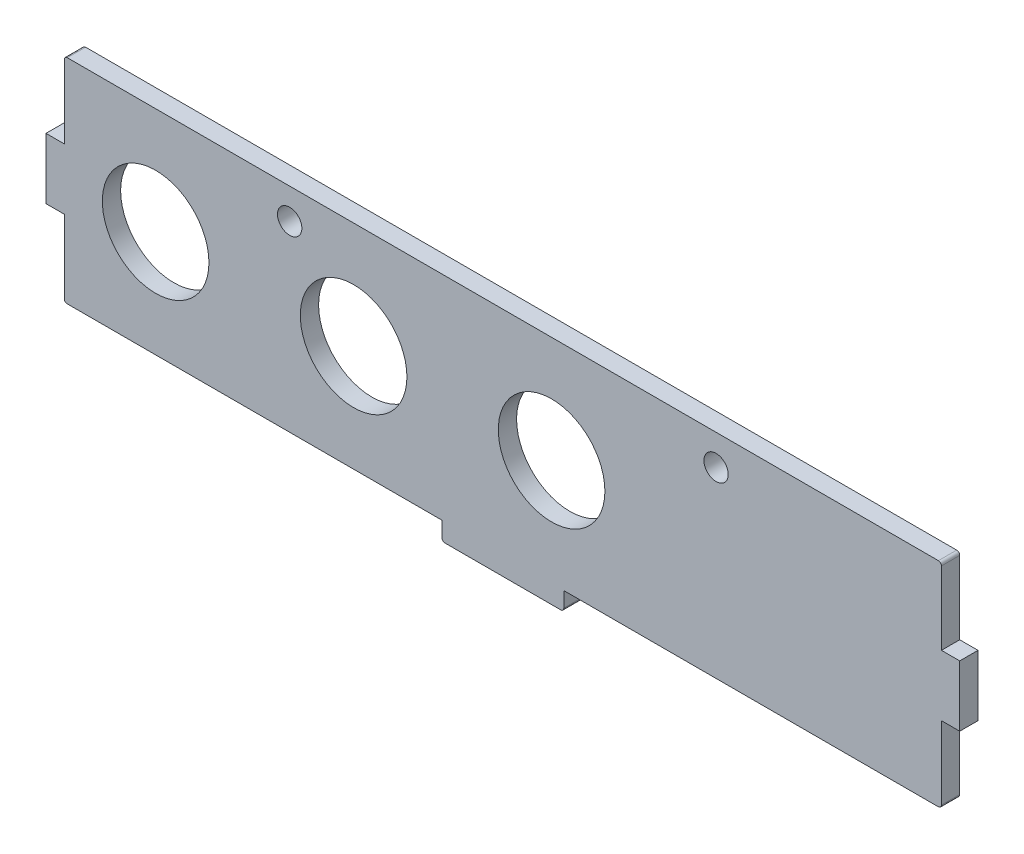
SolidWorks part; units mm, degrees
material "Beech"
ref_plane "Спереди" through (0, 0, 0) normal (0, 0, 1) x (1, 0, 0)
ref_plane "Сверху" through (0, 0, 0) normal (0, 1, 0) x (1, 0, 0)
ref_plane "Справа" through (0, 0, 0) normal (1, 0, 0) x (0, 0, -1)
sketch "Sketch1" plane through (0, 0, 0) normal (0, 0, 1) x (1, 0, 0)
  line L1 (0, 0) -> (300, 0)
  line L2 (0, 0) -> (0, 70)
  line L3 (0, 70) -> (300, 70)
  line L4 (300, 0) -> (300, 70)
  dimension "D1" = 70
  dimension "D2" = 300
extrude "front" add sketch "Sketch1" against normal blind 6
sketch "Sketch2" plane through (0, 0, 0) normal (0, 0, 1) x (1, 0, 0)
  line L0 (6, 70) -> (6, 45)
  line L1 (300, 70) -> (0, 70) construction
  line L2 (6, 45) -> (0, 45)
  line L3 (0, 70) -> (0, 0) construction
  line L4 (0, 25) -> (6, 25)
  line L5 (6, 25) -> (6, 0)
  line L6 (0, 0) -> (300, 0) construction
  line L7 (0, 45) -> (0, 25)
  line L8 (6, 70) -> (0, 70)
  line L9 (0, 70) -> (0, 45)
  line L10 (80, 60) -> (220, 60) construction
  line L11 (0, 25) -> (0, 0)
  line L12 (0, 0) -> (6, 0)
  line L13 (294, 70) -> (294, 45)
  line L14 (294, 45) -> (300, 45)
  line L15 (300, 0) -> (300, 70) construction
  line L16 (300, 45) -> (300, 70)
  line L17 (300, 70) -> (294, 70)
  line L18 (300, 25) -> (294, 25)
  line L19 (294, 25) -> (294, 0)
  line L20 (294, 0) -> (300, 0)
  line L21 (300, 0) -> (300, 25)
  circle A0 centre (80, 60) radius 4
  circle A1 centre (220, 60) radius 4
  point P32 (150, 60)
  point P33 (150, 70)
  line M1 (0, 70) -> (0, 0)
  line M2 (0, 0) -> (300, 0)
  line M4 (300, 70) -> (0, 70)
  dimension "D3" = 8
  dimension "D4" = 10
  dimension "D1" = 6
  dimension "D2" = 20
  dimension "D5" = 140
extrude "mount" cut sketch "Sketch2" against normal through all contours L2 L0 M4 M1 | L5 L4 M1 M2 | L16 L17 L13 L14 | L21 L18 L19 L20 | A0 | A1 region at (3, 12.5, 0) region at (3, 57.5, 0)
sketch "Sketch4" plane through (0, 0, 0) normal (0, 0, 1) x (1, 0, 0)
  line L0 (6, 0) -> (294, 0) construction
  line L1 (130, 0) -> (170, 0)
  line L2 (130, 0) -> (130, -6)
  line L3 (130, -6) -> (170, -6)
  line L4 (170, 0) -> (170, -6)
  line L5 (294, 70) -> (6, 70) construction
  point P6 (150, -6)
  point P7 (150, 70)
  dimension "D1" = 6
  dimension "D2" = 40
extrude "Boss-Extrude1" add sketch "Sketch4" against normal up to surface (6 mm away) up to face at (224, 60, -6)
fillet "fillet" radius 1 6 edges at (294, 0, -3) (294, 70, -3) (6, 0, -3) (6, 70, -3) (170, -6, -3) (130, -6, -3)
sketch "Sketch3" plane through (0, 0, 0) normal (0, 0, 1) x (1, 0, 0)
  line L0 (-29, 35) -> (36, 35) construction
  line L1 (36, 35) -> (101, 35) construction
  line L2 (101, 35) -> (166, 35) construction
  line L3 (7, 0) -> (130, 0) construction
  circle A0 centre (-29, 35) radius 17.5
  circle A1 centre (36, 35) radius 17.5
  circle A2 centre (101, 35) radius 17.5
  circle A3 centre (166, 35) radius 17.5
  point P8 (68.5, 35)
  point P9 (68.5, 0)
  dimension "D2" = 35
  dimension "D3" = 35
  dimension "D1" = 65
extrude "lite" cut sketch "Sketch3" against normal through all
